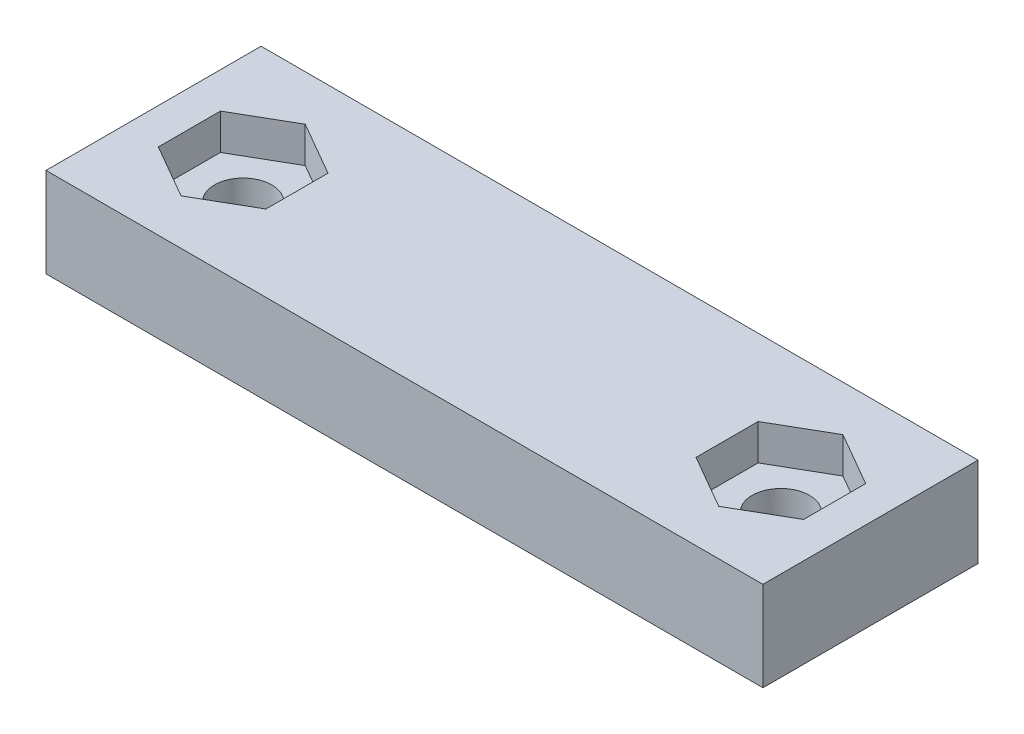
SolidWorks part; units mm, degrees
ref_plane "Front Plane" through (0, 0, 0) normal (0, 0, 1) x (1, 0, 0)
ref_plane "Top Plane" through (0, 0, 0) normal (0, 1, 0) x (1, 0, 0)
ref_plane "Right Plane" through (0, 0, 0) normal (1, 0, 0) x (0, 0, -1)
sketch "Sketch1" plane through (0, 0, 0) normal (0, 1, 0) x (1, 0, 0)
  line L1 (-20, 6) -> (20, 6)
  line L2 (-20, 6) -> (-20, -6)
  line L3 (-20, -6) -> (20, -6)
  line L4 (20, 6) -> (20, -6)
  line L5 (-20, 6) -> (20, -6) construction
  line L6 (-20, -6) -> (20, 6) construction
  point P0 (0, 0)
  dimension "D1" = 40
  dimension "D2" = 12
extrude "Boss-Extrude1" add sketch "Sketch1" along normal blind 5
sketch "Sketch2" plane through (0, 5, 0) normal (0, 1, 0) x (1, 0, 0)
  line L0 (-20, 0) -> (20, 0) construction
  line L1 (-20, 6) -> (-20, -6) construction
  line L2 (20, -6) -> (20, 6) construction
  line L3 (0, -6) -> (0, 7.5) construction
  line L4 (-20, -6) -> (20, -6) construction
  line L5 (20, 6) -> (-20, 6) construction
  circle A0 centre (15, 0) radius 1.6
  circle A1 centre (-15, 0) radius 1.6
  point P17 (0, 6)
  dimension "D1" = 3.2
  dimension "D2" = 15
extrude "Cut-Extrude2" cut sketch "Sketch2" against normal through all
sketch "Sketch3" plane through (-20, 0, 0) normal (-1, 0, 0) x (0, 0, 1)
  line L0 (-5.25, 1) -> (-5.25, 0)
  line L2 (-5.25, 0) -> (-4.25, 0)
  line L3 (-4.25, 0) -> (-4.25, 1)
  line L4 (-4.25, 1) -> (-5.25, 1)
  line L5 (-3.25, 0) -> (-2.25, 0)
  line L6 (-3.25, 1) -> (-3.25, 0)
  line L7 (-2.25, 0) -> (-2.25, 1)
  line L8 (-2.25, 1) -> (-3.25, 1)
  line L9 (-1.25, 0) -> (-0.25, 0)
  line L10 (-1.25, 1) -> (-1.25, 0)
  line L11 (-0.25, 0) -> (-0.25, 1)
  line L12 (-0.25, 1) -> (-1.25, 1)
  line L13 (0.75, 0) -> (1.75, 0)
  line L14 (0.75, 1) -> (0.75, 0)
  line L15 (1.75, 0) -> (1.75, 1)
  line L16 (1.75, 1) -> (0.75, 1)
  line L17 (2.75, 0) -> (3.75, 0)
  line L18 (2.75, 1) -> (2.75, 0)
  line L19 (3.75, 0) -> (3.75, 1)
  line L20 (3.75, 1) -> (2.75, 1)
  line L21 (4.75, 0) -> (5.75, 0)
  line L22 (4.75, 1) -> (4.75, 0)
  line L23 (5.75, 0) -> (5.75, 1)
  line L24 (5.75, 1) -> (4.75, 1)
  line L25 (6.75, 0) -> (7.75, 0)
  line L26 (6.75, 1) -> (6.75, 0)
  line L27 (7.75, 0) -> (7.75, 1)
  line L28 (7.75, 1) -> (6.75, 1)
  line L29 (8.75, 0) -> (9.75, 0)
  line L30 (8.75, 1) -> (8.75, 0)
  line L31 (9.75, 0) -> (9.75, 1)
  line L32 (9.75, 1) -> (8.75, 1)
  line L33 (-6, 5) -> (-6, 0) construction
  line L34 (-6, 0) -> (6, 0) construction
  dimension "D1" = 1
  dimension "D3" = 0.75
  dimension "D4" = 1
  dimension "D5" = 1
  dimension "D6" = 0
  dimension "D7" = 1
  dimension "D2" = 8
extrude "Teeth" cut sketch "Sketch3" against normal blind 5 and the other way blind 5 from surface starting at plane "Right Plane"
sketch "Sketch4" plane through (0, 5, 0) normal (0, 1, 0) x (1, 0, 0)
  line L0 (-15, 0) -> (-15, 3.4641) construction
  line L1 (-15, 3.4641) -> (-18, 1.7321)
  line L2 (-18, 1.7321) -> (-18, -1.7321)
  line L3 (-18, -1.7321) -> (-15, -3.4641)
  line L4 (-15, -3.4641) -> (-12, -1.7321)
  line L5 (-12, -1.7321) -> (-12, 1.7321)
  line L6 (-12, 1.7321) -> (-15, 3.4641)
  line L7 (0, 6) -> (0, -7.5) construction
  line L8 (20, 6) -> (-20, 6) construction
  line L10 (15, 0) -> (15, 3.4641) construction
  line L11 (12, 1.7321) -> (15, 3.4641)
  line L12 (12, -1.7321) -> (12, 1.7321)
  line L13 (15, -3.4641) -> (12, -1.7321)
  line L14 (18, -1.7321) -> (15, -3.4641)
  line L15 (18, 1.7321) -> (18, -1.7321)
  line L16 (15, 3.4641) -> (18, 1.7321)
  line L17 (-15, 0) -> (-15, 3.4641) construction
  circle A0 centre (-15, 0) radius 3 construction
  circle A1 centre (15, 0) radius 3 construction
  dimension "D1" = 6
extrude "Cut-Extrude4" cut sketch "Sketch4" against normal blind 2
equation "\"X-ROD-SPACING\"=45"
equation "\"Y-ROD-SPACING\"=75"
equation "\"Z-ROD-SPACING\"=17.5"
equation "\"Y-BED-OFFSET\"=2"
equation "\"Y-BED-ROD-INSET\"=3.5"
equation "\"T-SLOT-NUT-FILLET-RADIUS\"=0.25"
equation "\"T-SLOT-SCREW-SHAFT-RADIUS\"=1.75"
equation "\"T-SLOT-SCREW-SHAFT-CUTOUT-LENGTH\"=10.5"
equation "\"T-SLOT-NUT-DEPTH\"=4.2"
equation "\"T-SLOT-NUT-WIDTH\"=3"
equation "\"T-SLOT-NUT-END-DISTANCE\"=8"
equation "\"ACRYLIC-THICKNESS\"=10"
equation "\"ACRYLIC-THICKNESS2\"=4.5"
equation "\"ACRYLIC-TAB-CUTOUT-SIZE\"=\"ACRYLIC-THICKNESS\"+\"ACRYLIC-TAB-TOLERANCE\"*2"
equation "\"ACRYLIC-TAB-WIDTH\"=\"ACRYLIC-THICKNESS\""
equation "\"ACRYLIC-M3-HOLE\"=3.2"
equation "\"SMOOTHROD-CAP-SCREW-DISTANCE\"=20"
equation "\"FRAME-WIDTH-INNER\"=370"
equation "\"NEMA17-HOLE-SPACING\"=31"
equation "\"NEMA17-CENTRAL-CUTOUT\"=22.5"
equation "\"Z-BRACKET-REACH\"=55"
equation "\"TOP-BRACKET-SPACING\"=40"
equation "\"SMOOTHROD-X-LENGTH\"=350"
equation "\"SMOOTHROD-Y-LENGTH\"=350"
equation "\"SMOOTHROD-Z-LENGTH\"=350"
equation "\"SMOOTHROD-TIGHTENING-HEADROOM\"=1"
equation "\"LEADSCREW-Z-LENGTH\"=300"
equation "\"SCREW-LENGTH-FRAME\"=\"ACRYLIC-THICKNESS\" + 10"
equation "\"SCREW-HEAD-RADIUS\"=6"
equation "\"PRINTED-X-SMOOTHROD-DIAMETER\"=8.2"
equation "\"PRINTED-X-SMOOTHROD-CUTOUT\"=10"
equation "\"PRINTED-X-BASE-HEIGHT\"=10"
equation "\"PRINTED-LM8UU-CUTOUT-SIZE\"=16"
equation "\"PRINTED-LM8UU-CUTOUT-LENGTH\"=24.5"
equation "\"PRINTED-X-IDLER-HEIGHT\"=16"
equation "\"PSU-MOUNTING-WIDTH\"=95"
equation "\"PSU-MOUNTING-HEIGHT\"=177"
equation "\"Y-BELT-TO-ROD-DISTANCE\"=20"
equation "\"D1@Sketch4\"=\"T-SLOT-NUT-WIDTH\"*2"
